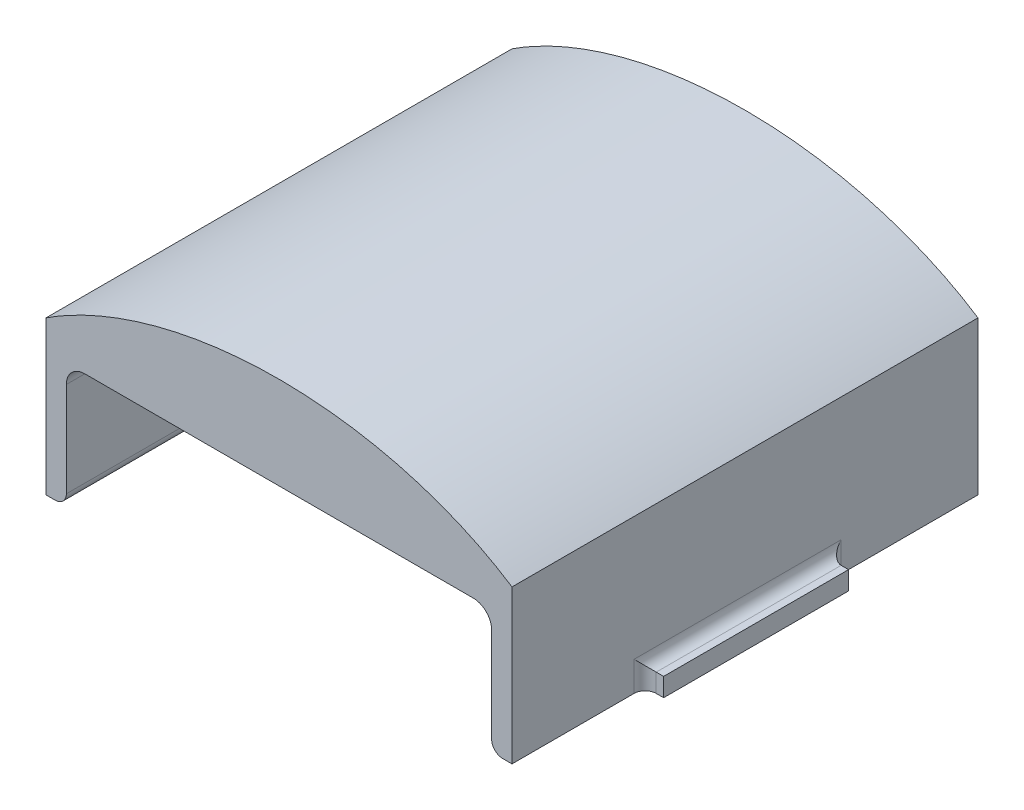
SolidWorks part; units mm, degrees
ref_plane "Front Plane" through (0, 0, 0) normal (0, 0, 1) x (1, 0, 0)
ref_plane "Top Plane" through (0, 0, 0) normal (0, 1, 0) x (1, 0, 0)
ref_plane "Right Plane" through (0, 0, 0) normal (1, 0, 0) x (0, 0, -1)
sketch "Sketch1" plane through (0, 0, 0) normal (0, 0, 1) x (1, 0, 0)
  ellipse E0 centre (0, 0) end of major axis (-22.86, 0) minor radius 15.24
extrude "Boss-Extrude4" add sketch "Sketch1" along normal blind 45.72 contours E0
sketch "Sketch4" plane through (0, 0, 45.72) normal (0, 0, 1) x (1, 0, 0)
  line L1 (14.605, -8.89) -> (-14.605, -8.89)
  line L2 (14.605, -8.89) -> (14.605, 8.89)
  line L3 (14.605, 8.89) -> (-14.605, 8.89)
  line L4 (-14.605, -8.89) -> (-14.605, 8.89)
  dimension "D1" = 8.89
  dimension "D2" = 17.78
  dimension "D3" = 14.605
  dimension "D4" = 29.21
extrude "Cut-Extrude2" cut sketch "Sketch4" against normal blind 33.02 from offset 10.16 offset against normal yes
sketch "Sketch7" plane through (0, 0, 0) normal (1, 0, 0) x (0, 0, -1)
  line L0 (-45.72, 15.24) -> (-45.72, -15.24) construction
  line L1 (-38.1, 16.1024) -> (-52.7439, 16.1024)
  line L2 (-38.1, 16.1024) -> (-38.1, -19.4576)
  line L3 (-38.1, -19.4576) -> (-52.7439, -19.4576)
  line L4 (-52.7439, 16.1024) -> (-52.7439, -19.4576)
  dimension "D1" = 7.62
  dimension "D2" = 14.6439
  dimension "D3" = 35.56
extrude "Cut-Extrude4" cut sketch "Sketch7" against normal blind 33.02 and the other way blind 33.02
sketch "Sketch8" plane through (0, 0, 0) normal (0, 0, 1) x (1, 0, 0)
  circle A0 centre (0, 0) radius 1.75
  circle A1 centre (4.064, 0) radius 1.75
  circle A2 centre (-4.064, 0) radius 1.75
extrude "Cut-Extrude5" cut sketch "Sketch8" along normal blind 1.27
sketch "Sketch9" plane through (0, 0, 0) normal (0, 0, -1) x (-1, 0, 0)
  circle A0 centre (0, 0.8) radius 0.5
  circle A1 centre (0, -0.8) radius 0.5
  circle A2 centre (-4.064, 0.8) radius 0.5
  circle A3 centre (-4.064, -0.8) radius 0.5
  circle A4 centre (4.064, 0.8) radius 0.5
  circle A5 centre (4.064, -0.8) radius 0.5
extrude "Cut-Extrude7" cut sketch "Sketch9" against normal blind 2.794
fillet "Fillet1" radius 1.27 1 edges at (-22.86, 0, 0)
fillet "Fillet2" radius 1.27 1 edges at (-22.86, 0, 38.1)
sketch "Sketch10" plane through (0, 0, 0) normal (0, 0, -1) x (-1, 0, 0)
  line L1 (-22.86, 0) -> (22.86, 0)
  line L2 (-22.86, 0) -> (-22.86, -17.78)
  line L3 (-22.86, -17.78) -> (22.86, -17.78)
  line L4 (22.86, 0) -> (22.86, -17.78)
  ellipse E0 centre (0, 0) end of major axis (22.86, 0) minor radius 15.24 construction
  dimension "D1" = 22.86
  dimension "D2" = 45.72
  dimension "D3" = 17.78
extrude "Cut-Extrude8" cut sketch "Sketch10" against normal through all
sketch "Sketch11" plane through (0, 0, 0) normal (0, 0, -1) x (-1, 0, 0)
  line L2 (22.86, 0) -> (-22.86, 0)
  line L3 (22.86, 0) -> (22.86, 2.1336)
  line L4 (22.86, 2.1336) -> (-22.86, 2.1336)
  line L5 (-22.86, 0) -> (-22.86, 2.1336)
  ellipse E0 centre (0, 0) end of major axis (22.86, 0) minor radius 15.24 (22.86, 0) -> (-22.86, 0) ccw construction
  dimension "D1" = 0
sketch "Sketch13" plane through (0, 0, 0) normal (0, -1, 0) x (1, 0, 0)
  line L0 (-22.86, 0) -> (22.86, 0) construction
  line L1 (16.002, 3.048) -> (-16.002, 3.048)
  line L2 (16.002, 3.048) -> (16.002, 35.052)
  line L3 (16.002, 35.052) -> (-16.002, 35.052)
  line L4 (-16.002, 3.048) -> (-16.002, 35.052)
  line L5 (21.59, 38.1) -> (-21.59, 38.1) construction
  line L6 (22.86, 36.83) -> (22.86, 1.27) construction
  line L7 (-22.86, 36.83) -> (-22.86, 1.27) construction
  line M5 (1.75, 1.27) -> (1.75, 0)
  line M6 (1.75, 0) -> (2.314, 0)
  line M7 (2.314, 0) -> (2.314, 1.27)
  line M8 (2.314, 1.27) -> (5.814, 1.27)
  line M9 (5.814, 1.27) -> (5.814, 0)
  line M10 (5.814, 0) -> (21.59, 0)
  arc M11 (21.59, 0) -> (22.86, 1.27) centre (21.59, 1.27) ccw
  line M12 (22.86, 1.27) -> (22.86, 36.83)
  arc M13 (22.86, 36.83) -> (21.59, 38.1) centre (21.59, 36.83) ccw
  line M14 (21.59, 38.1) -> (-21.59, 38.1)
  arc M15 (-21.59, 38.1) -> (-22.86, 36.83) centre (-21.59, 36.83) ccw
  line M16 (-22.86, 36.83) -> (-22.86, 1.27)
  arc M17 (-22.86, 1.27) -> (-21.59, 0) centre (-21.59, 1.27) ccw
  line M18 (-21.59, 0) -> (-5.814, 0)
  line M19 (-5.814, 0) -> (-5.814, 1.27)
  line M20 (-5.814, 1.27) -> (-2.314, 1.27)
  line M21 (-2.314, 1.27) -> (-2.314, 0)
  line M22 (-2.314, 0) -> (-1.75, 0)
  line M23 (-1.75, 0) -> (-1.75, 1.27)
  line M24 (-1.75, 1.27) -> (1.75, 1.27)
  line M25 (14.605, 2.54) -> (-14.605, 2.54)
  line M26 (-14.605, 2.54) -> (-14.605, 35.56)
  line M27 (-14.605, 35.56) -> (14.605, 35.56)
  line M28 (14.605, 35.56) -> (14.605, 2.54)
  dimension "D1" = 3.048
  dimension "D2" = 3.048
  dimension "D3" = 6.858
  dimension "D4" = 32.004
  dimension "D5" = 6.858
extrude "Cut-Extrude10" cut sketch "Sketch13" against normal through all contours L1 L4 L3 L2 M24 M5 M6 M7 M8 M9 M10 M11 M12 M13 M14 M15 M16 M17 M18 M19 M20 M21 M22 M23 M26 M27 M28 M25 region at (0, 0, 1.8651) body kept at (14.605, 11.7241, 3.048)
sketch "Sketch15" plane through (0, 0, 0) normal (0, 1, 0) x (1, 0, 0)
  line L1 (-14.605, -2.54) -> (14.605, -2.54)
  line L2 (-14.605, -2.54) -> (-14.605, -3.048)
  line L3 (-14.605, -3.048) -> (14.605, -3.048)
  line L4 (14.605, -2.54) -> (14.605, -3.048)
  line L5 (-14.605, -35.56) -> (14.605, -35.56)
  line L6 (-14.605, -35.56) -> (-14.605, -35.052)
  line L7 (-14.605, -35.052) -> (14.605, -35.052)
  line L8 (14.605, -35.56) -> (14.605, -35.052)
extrude "Cut-Extrude13" cut sketch "Sketch15" along normal through all contours L1 L4 L3 L2 | L7 L8 L5 L6
sketch "Sketch16" plane through (0, 0, 3.048) normal (0, 0, -1) x (-1, 0, 0)
  line L1 (-16.002, 0) -> (16.002, 0)
  line L2 (-16.002, 0) -> (-16.002, 0.3556)
  line L3 (-16.002, 0.3556) -> (16.002, 0.3556)
  line L4 (16.002, 0) -> (16.002, 0.3556)
  dimension "D1" = 0.3556
  dimension "D2" = 0
extrude "Cut-Extrude14" cut sketch "Sketch16" against normal through all
sketch "Sketch17" plane through (0, 0, 3.048) normal (0, 0, -1) x (-1, 0, 0)
  line L1 (-16.002, 0.3556) -> (-17.272, 0.3556)
  line L2 (-16.002, 0.3556) -> (-16.002, 1.6256)
  line L3 (-16.002, 1.6256) -> (-17.272, 1.6256)
  line L4 (-17.272, 0.3556) -> (-17.272, 1.6256)
  line L5 (16.002, 0.3556) -> (17.272, 0.3556)
  line L6 (16.002, 0.3556) -> (16.002, 1.6256)
  line L7 (16.002, 1.6256) -> (17.272, 1.6256)
  line L8 (17.272, 0.3556) -> (17.272, 1.6256)
  dimension "D1" = 1.27
  dimension "D2" = 1.27
  dimension "D3" = 1.27
  dimension "D4" = 1.27
extrude "Boss-Extrude5" add sketch "Sketch17" against normal blind 12.7 from offset 10.16 offset against normal yes
fillet "Fillet3" radius 0.762 3 edges at (16.002, 0.9906, 13.208) (16.002, 0.9906, 25.908) (16.002, 1.6256, 19.558)
fillet "Fillet4" radius 0.762 3 edges at (-16.002, 0.9906, 13.208) (-16.002, 1.6256, 19.558) (-16.002, 0.9906, 25.908)
fillet "Fillet5" radius 0.762 2 edges at (14.605, 0.3556, 19.05) (-14.605, 0.3556, 19.05)
fillet "Fillet6" radius 1.27 2 edges at (-14.605, 8.89, 19.05) (14.605, 8.89, 19.05)
